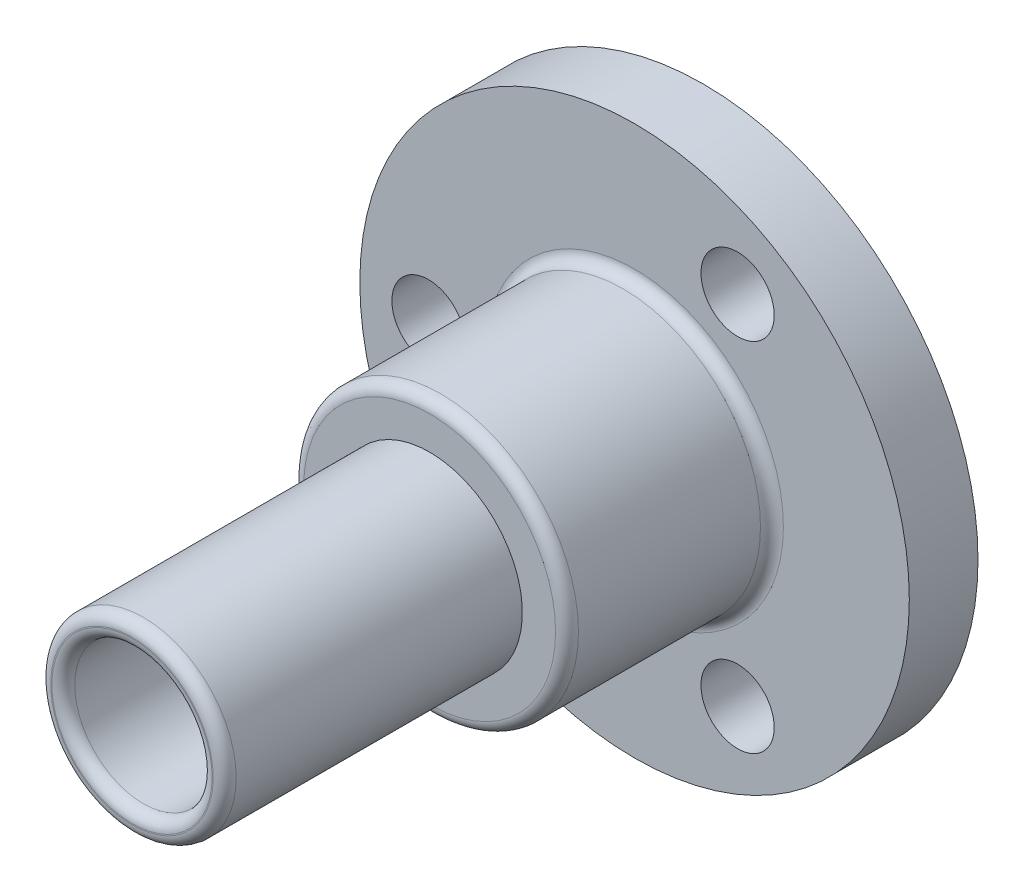
SolidWorks part; units mm, degrees
ref_plane "Alzado" through (0, 0, 0) normal (1, 0, 0) x (0, 1, 0)
ref_plane "Planta" through (0, 0, 0) normal (0, 0, 1) x (0, 1, 0)
ref_plane "Vista lateral" through (0, 0, 0) normal (0, 1, 0) x (-1, 0, 0)
sketch "Croquis1" plane through (0, 0, 0) normal (0, 0, 1) x (0, 1, 0)
  circle A0 centre (0, 0) radius 12
  circle A1 centre (0, 0) radius 9 construction
  circle A2 centre (0, 9) radius 1.6
  circle A3 centre (7.7942, -4.5) radius 1.6
  circle A4 centre (-7.7942, -4.5) radius 1.6
  circle A5 centre (0, 0) radius 4.5
  point P13 (0, 0)
  dimension "D1" = 24
  dimension "D2" = 18
  dimension "D3" = 3.2
  dimension "D5" = 9
  dimension "D4" = 3
extrude "Saliente-Extruir1" add sketch "Croquis1" along normal blind 3
sketch "Croquis2" plane through (0, 0, 3) normal (0, 0, 1) x (1, 0, 0)
  circle A0 centre (0, 0) radius 3
  circle A1 centre (0, 0) radius 6
  dimension "D1" = 6
  dimension "D2" = 12
extrude "Saliente-Extruir2" add sketch "Croquis2" along normal blind 8.95
sketch "Croquis3" plane through (0, 0, 11.95) normal (0, 0, 1) x (1, 0, 0)
  circle A0 centre (0, 0) radius 3
  circle A1 centre (0, 0) radius 4.05
  dimension "D1" = 8.1
  dimension "D2" = 6
extrude "Saliente-Extruir3" add sketch "Croquis3" along normal blind 13
fillet "Redondeo1" radius 0.5 4 edges at (3, 0, 24.95) (4.05, 0, 24.95) (6, 0, 11.95) (6, 0, 3)
